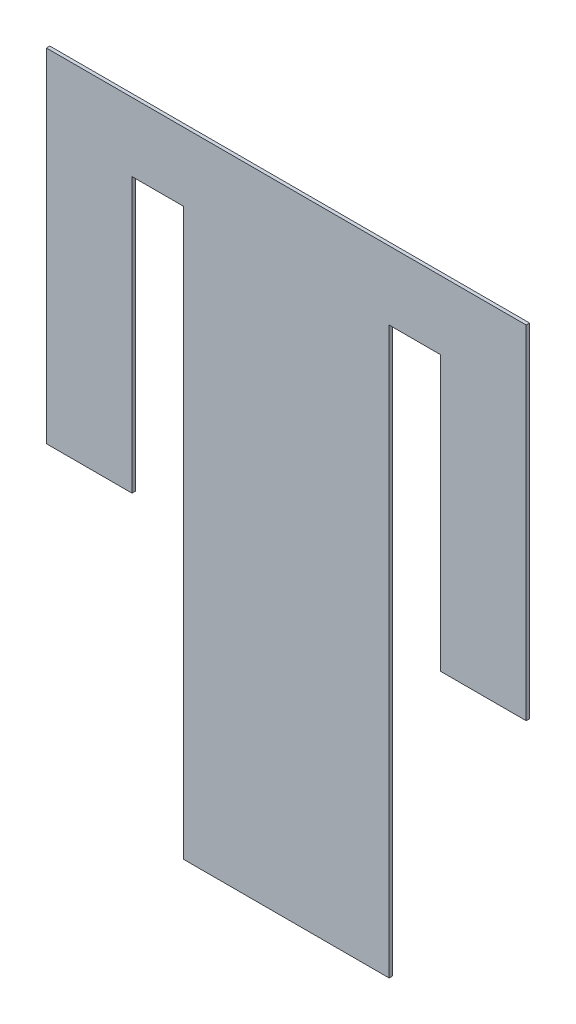
SolidWorks part; units mm, degrees
ref_plane "Front Plane" through (0, 0, 0) normal (0, 0, 1) x (1, 0, 0)
ref_plane "Top Plane" through (0, 0, 0) normal (0, 1, 0) x (1, 0, 0)
ref_plane "Right Plane" through (0, 0, 0) normal (1, 0, 0) x (0, 0, -1)
sketch "Sketch1" plane through (0, 0, 0) normal (0, 0, 1) x (1, 0, 0)
  line L0 (0, 0) -> (0, 200)
  line L5 (0, 200) -> (280, 200)
  line L6 (280, 200) -> (280, 0)
  line L11 (280, 0) -> (230, 0)
  line L12 (230, 0) -> (230, 160)
  line L13 (230, 160) -> (200, 160)
  line L14 (200, 160) -> (200, -170)
  line L15 (200, -170) -> (80, -170)
  line L16 (80, -170) -> (80, 160)
  line L17 (80, 160) -> (50, 160)
  line L18 (50, 160) -> (50, 0)
  line L19 (50, 0) -> (0, 0)
  dimension "D1" = 280
  dimension "D2" = 200
  dimension "D3" = 120
  dimension "D4" = 30
  dimension "D6" = 50
  dimension "D8" = 330
  dimension "15" = 160
extrude "Boss-Extrude1" add sketch "Sketch1" along normal blind 2
